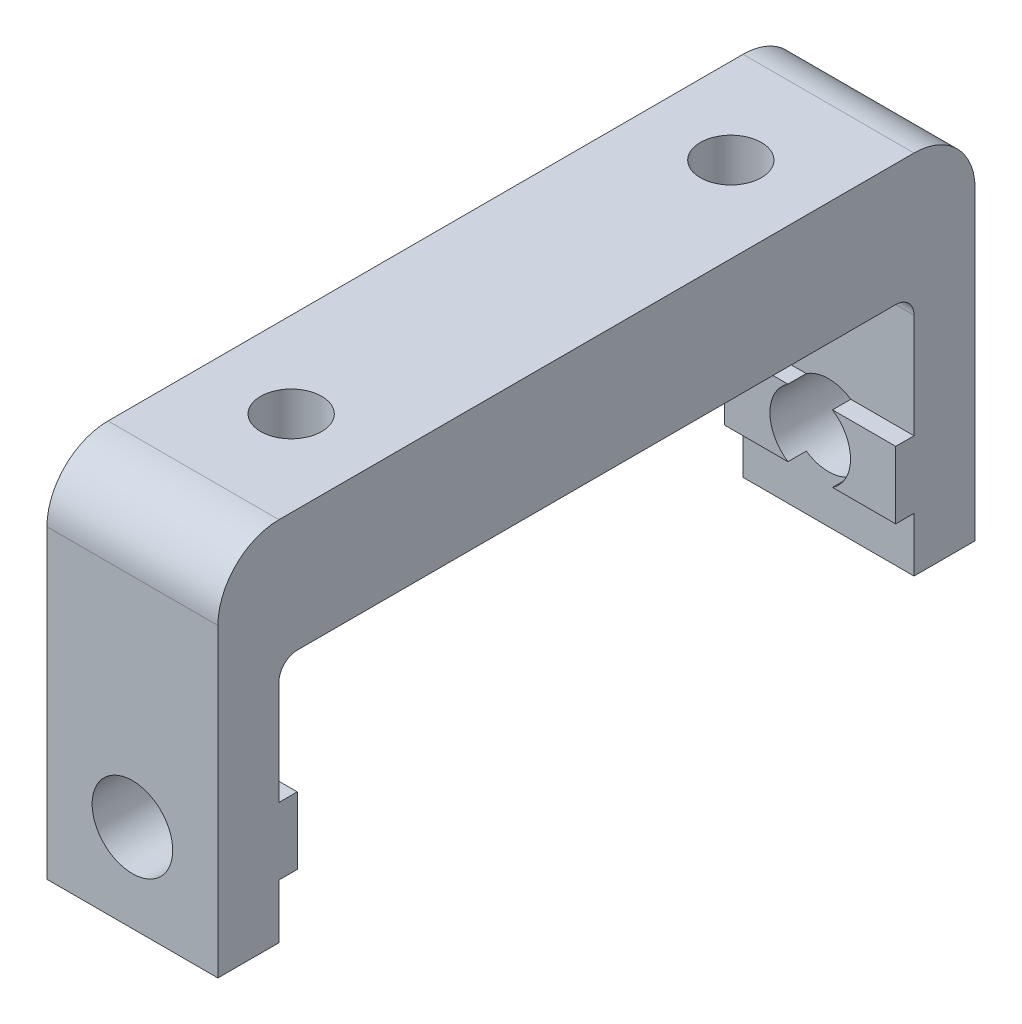
SolidWorks part; units mm, degrees
ref_plane "Front Plane" through (0, 0, 0) normal (0, 0, 1) x (1, 0, 0)
ref_plane "Top Plane" through (0, 0, 0) normal (0, 1, 0) x (1, 0, 0)
ref_plane "Right Plane" through (0, 0, 0) normal (1, 0, 0) x (0, 0, -1)
sketch "Sketch1" plane through (0, 0, 0) normal (1, 0, 0) x (0, 0, -1)
  line L0 (0, 0) -> (-31, 0)
  line L1 (-31, 0) -> (-31, -30)
  line L2 (-31, -30) -> (-26, -30)
  line L3 (-26, -30) -> (-26, -10)
  line L4 (-26, -10) -> (0, -10)
  line L5 (0, -10) -> (0, 0)
  point P7 (-28.5, -30)
  dimension "D1" = 10
  dimension "D2" = 5
  dimension "D3" = 26
  dimension "D4" = 20
extrude "Boss-Extrude1" add sketch "Sketch1" along normal blind 14
sketch "Sketch4" plane through (0, 0, 26) normal (0, 0, -1) x (-1, 0, 0)
  line L0 (-14, -30) -> (-14, -10) construction
  line L1 (-14, -20.05) -> (0, -20.05)
  line L2 (-14, -20.05) -> (-14, -25.55)
  line L3 (-14, -25.55) -> (0, -25.55)
  line L4 (0, -20.05) -> (0, -25.55)
  line L5 (0, -30) -> (0, -10) construction
  line L6 (-7, -20.05) -> (-7, -25.55) construction
  point P14 (-14, -22.8)
  dimension "D1" = 5.5
  dimension "D2" = 12.8
extrude "Boss-Extrude3" add sketch "Sketch4" along normal blind 1.5
sketch "Sketch2" plane through (0, 0, 31) normal (0, 0, 1) x (1, 0, 0)
  line L0 (0, -22.8) -> (14, -22.8) construction
  line L1 (0, 0) -> (0, -30) construction
  line L2 (14, 0) -> (14, -30) construction
  line L5 (14, -20.05) -> (14, -25.55) construction
  circle A0 centre (7, -22.8) radius 3.3
  point P12 (14, -22.8)
  dimension "D1" = 6.6
extrude "Cut-Extrude1" cut sketch "Sketch2" against normal up to next and the other way through all
fillet "Fillet1" radius 5 1 edges at (7, 0, 31)
fillet "Fillet2" radius 1.5 1 edges at (7, -10, 26)
sketch "Sketch7" plane through (0, -10, 0) normal (0, 1, 0) x (1, 0, 0)
  line L0 (7, 0) -> (7, -26) construction
  line L3 (14, 0) -> (0, 0) construction
  line L5 (0, -26) -> (14, -26) construction
  circle A2 centre (7, -18) radius 2.5
  circle A3 centre (7, -18) radius 4.5
  dimension "D1" = 5
  dimension "D3" = 9
  dimension "D2" = 18
extrude "Cut-Extrude4" cut sketch "Sketch7" along normal through all contours A2
extrude "Cut-Extrude5" cut sketch "Sketch7<3>" along normal blind 4.6
sketch "Sketch7<3>" plane through (0, -10, 0) normal (0, 1, 0) x (1, 0, 0) same geometry as "Sketch7"
mirror "Mirror1" about plane through (0, 0, 0) normal (0, 0, 1) of "Cut-Extrude5", "Cut-Extrude4", "Boss-Extrude3", "Fillet2", "Fillet1", "Cut-Extrude1", "Boss-Extrude1"
